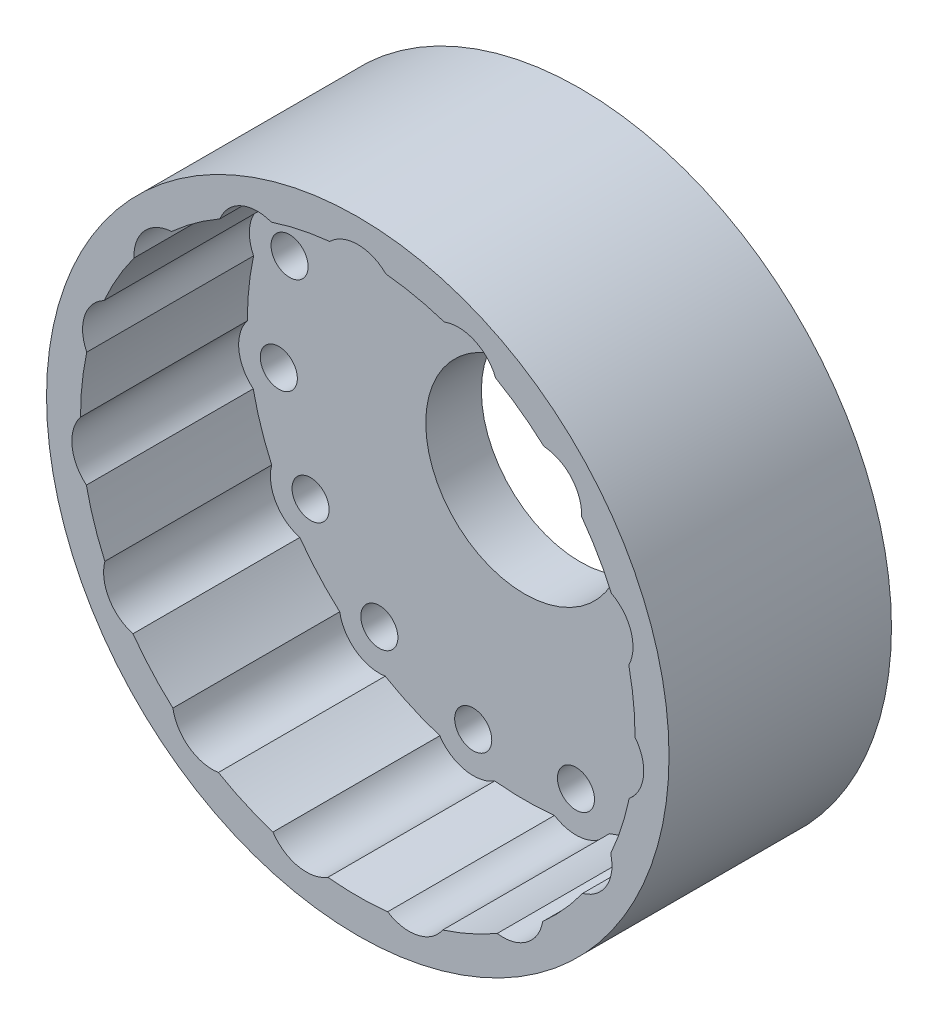
SolidWorks part; units mm, degrees
ref_plane "Front Plane" through (0, 0, 0) normal (0, 0, 1) x (1, 0, 0)
ref_plane "Top Plane" through (0, 0, 0) normal (0, 1, 0) x (1, 0, 0)
ref_plane "Right Plane" through (0, 0, 0) normal (1, 0, 0) x (0, 0, -1)
sketch "Sketch1" plane through (0, 0, 0) normal (0, 0, 1) x (1, 0, 0)
  circle A0 centre (0, 0) radius 40
  circle A1 centre (0, 40) radius 6.5
  circle A2 centre (0, 0) radius 44.875
  circle A3 centre (0, 0) radius 50.375
  dimension "D1" = 80
  dimension "D2" = 13
  dimension "D3" = 0
  dimension "D4" = 4.875
  dimension "D5" = 5.5
extrude "Boss-Extrude1" add sketch "Sketch1" along normal blind 9 contours A1 A0 | A0 A1 | A1 A2 A0 | A1 A2 A0 | A2 A1 | A3 A2 A1 region at (0, -0.4797, 0) region at (31.4551, 26.7132, 0) region at (0, 37.1484, 0) region at (0, 42.1673, 0) region at (0, 45.4868, 0) region at (-48.9502, 0, 0)
sketch "Sketch2" plane through (0, 0, 9) normal (0, 0, 1) x (1, 0, 0)
  circle A0 centre (0, 0) radius 50.375 construction
  circle A1 centre (0, 0) radius 44.875 construction
  circle A2 centre (0, 40) radius 6.5 construction
  circle A3 centre (0, 0) radius 50.375
  circle A4 centre (0, 0) radius 44.875
  circle A5 centre (0, 40) radius 6.5
  circle A6 centre (16.2695, 36.5418) radius 6.5
  circle A7 centre (29.7258, 26.7652) radius 6.5
  circle A8 centre (38.0423, 12.3607) radius 6.5
  circle A9 centre (39.7809, -4.1811) radius 6.5
  circle A10 centre (34.641, -20) radius 6.5
  circle A11 centre (23.5114, -32.3607) radius 6.5
  circle A12 centre (8.3165, -39.1259) radius 6.5
  circle A13 centre (-8.3165, -39.1259) radius 6.5
  circle A14 centre (-23.5114, -32.3607) radius 6.5
  circle A15 centre (-34.641, -20) radius 6.5
  circle A16 centre (-39.7809, -4.1811) radius 6.5
  circle A17 centre (-38.0423, 12.3607) radius 6.5
  circle A18 centre (-29.7258, 26.7652) radius 6.5
  circle A19 centre (-16.2695, 36.5418) radius 6.5
  point P38 (0, 0)
  circle M6 centre (0, 0) radius 50.375
  dimension "D1" = 15
extrude "Boss-Extrude2" add sketch "Sketch2" along normal blind 27 contours A19 A4 A5 A6 A7 A8 A9 A10 A11 A12 A13 A14 A15 A16 A17 A18 M6 region at (-48.9502, 0, 9)
sketch "Sketch3" plane through (0, 0, 9) normal (0, 0, 1) x (1, 0, 0)
  circle A0 centre (0, 40) radius 6.5 construction
  circle A1 centre (0, 40) radius 6.5 construction
  circle A2 centre (0, 40) radius 3
  circle A3 centre (16.2695, 36.5418) radius 3
  circle A4 centre (29.7258, 26.7652) radius 3
  circle A5 centre (38.0423, 12.3607) radius 3
  circle A6 centre (39.7809, -4.1811) radius 3
  circle A7 centre (34.641, -20) radius 3
  circle A8 centre (23.5114, -32.3607) radius 3
  circle A9 centre (8.3165, -39.1259) radius 3
  circle A10 centre (-8.3165, -39.1259) radius 3
  circle A11 centre (-23.5114, -32.3607) radius 3
  circle A12 centre (-34.641, -20) radius 3
  circle A13 centre (-39.7809, -4.1811) radius 3
  circle A14 centre (-38.0423, 12.3607) radius 3
  circle A15 centre (-29.7258, 26.7652) radius 3
  circle A16 centre (-16.2695, 36.5418) radius 3
  point P34 (0, 0)
  dimension "D1" = 6
  dimension "D2" = 15
extrude "Cut-Extrude3" cut sketch "Sketch3" against normal blind 5
sketch "Sketch4" plane through (0, 0, 9) normal (0, 0, 1) x (1, 0, 0)
  circle A0 centre (0, 0) radius 16
  dimension "D1" = 32
extrude "Cut-Extrude4" cut sketch "Sketch4" against normal through all
equation "\"roller_radius\"= 6.5"
equation "\"eccentricity\"= \"roller_radius\" * 0.325"
equation "\"outer_radius\"= 40"
equation "\"eccentric_shaft_radius\"= 16"
equation "\"rotor_width\"= 10"
equation "\"housing_depth\"= 40"
equation "\"bottom_depth\"= 5"
equation "\"roller_bearing_OD\"= \"roller_radius\" * 2"
equation "\"roller_bearing_ID\"= 6"
equation "\"eccentric_bearing_ID\"= 6"
equation "\"eccentric_bearing_OD\"= 15"
equation "\"roller_bearing_height\"= 5"
equation "\"eccentric_bearing_height\"= 5"
equation "\"bottom_bearing_ID\"= 15"
equation "\"bottom_bearing_OD\"= 32"
equation "\"bottom_bearing_height\"= 9"
equation "\"distance_to_output_rotor_holes\"= 20"
equation "\"D1@Sketch1\"=\"outer_radius\"*2"
equation "\"D2@Sketch1\"=\"roller_bearing_OD\""
equation "\"D4@Sketch1\"=\"roller_radius\"*0.75"
equation "\"D1@Sketch3\"=\"roller_bearing_ID\""
equation "\"D1@Sketch4\"=\"bottom_bearing_OD\""
equation "\"D1@Boss-Extrude1\"=\"bottom_bearing_height\""
equation "\"D5@Sketch1\"=\"D1@Sketch1\"*0.06875"
equation "\"output_bearing_ID\" = 25"
equation "\"output_bearing_OD\" = 37"
equation "\"output_bearing_height\" = 7"
equation "\"number_of_rollers\" = 15"
equation "\"housing_height\" = 27"
equation "\"spacer_1\" = 7"
equation "\"spacer_2\" = 2.5"
equation "\"spacer_3\" = 7.5"
equation "\"D1@Boss-Extrude2\"=\"roller_bearing_height\"*2+\"spacer_1\"+\"spacer_2\"+\"spacer_3\""
equation "\"roller_pin_depth\" = 5"
equation "\"D1@Cut-Extrude3\"=\"roller_pin_depth\""
